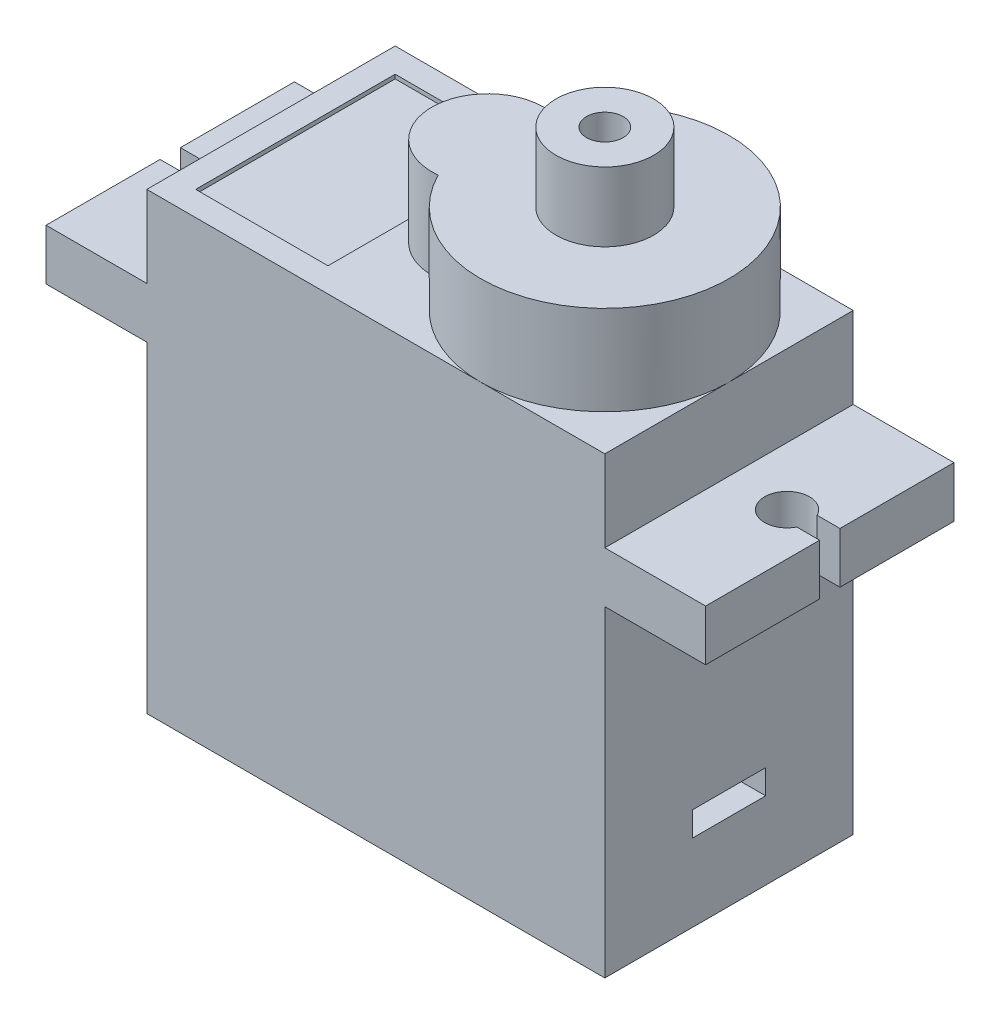
SolidWorks part; units mm, degrees
ref_plane "前视基准面" through (0, 0, 0) normal (0, 0, 1) x (1, 0, 0)
ref_plane "上视基准面" through (0, 0, 0) normal (0, 1, 0) x (1, 0, 0)
ref_plane "右视基准面" through (0, 0, 0) normal (1, 0, 0) x (0, 0, -1)
other "Configuration Table"
sketch "草图1" plane through (0, 0, 0) normal (0, 0, 1) x (1, 0, 0)
  line L0 (-11.25, 0) -> (11.25, 0)
  line L1 (11.25, 0) -> (11.25, 15.8)
  line L2 (11.25, 15.8) -> (16.2, 15.8)
  line L3 (16.2, 15.8) -> (16.2, 18.3)
  line L4 (16.2, 18.3) -> (11.25, 18.3)
  line L5 (11.25, 18.3) -> (11.25, 22.3)
  line L6 (11.25, 22.3) -> (-11.25, 22.3)
  line L7 (-11.25, 22.3) -> (-11.25, 18.3)
  line L8 (-11.25, 18.3) -> (-16.2, 18.3)
  line L9 (-16.2, 18.3) -> (-16.2, 15.8)
  line L10 (-16.2, 15.8) -> (-11.25, 15.8)
  line L11 (-11.25, 15.8) -> (-11.25, 0)
  line L12 (0, 22.3) -> (0, 0) construction
  point P20 (16.2, 17.05)
  dimension "D1" = 22.3
  dimension "D2" = 22.5
  dimension "D3" = 2.5
  dimension "D4" = 32.4
  dimension "D5" = 4
extrude "凸台-拉伸1" add sketch "草图1" along normal blind 12.2
sketch "草图3" plane through (11.25, 0, 0) normal (1, 0, 0) x (0, 0, -1)
  line L0 (-12.2, 0) -> (0, 0) construction
  line L1 (-7.9, 5) -> (-4.3, 5)
  line L2 (-7.9, 5) -> (-7.9, 3.8)
  line L3 (-7.9, 3.8) -> (-4.3, 3.8)
  line L4 (-4.3, 5) -> (-4.3, 3.8)
  line L5 (-6.1, 15.8) -> (-6.1, 0) construction
  line L6 (-12.2, 15.8) -> (0, 15.8) construction
  point P10 (-6.1, 5)
  dimension "D1" = 5
  dimension "D2" = 1.2
  dimension "D3" = 3.6
extrude "切除-拉伸1" cut sketch "草图3" against normal blind 2
sketch "草图4" plane through (0, 22.3, 0) normal (0, 1, 0) x (1, 0, 0)
  line L0 (11.25, 0) -> (-11.25, 0) construction
  line L1 (11.25, -12.2) -> (-11.25, -12.2) construction
  line L2 (11.25, -12.2) -> (11.25, 0) construction
  line L3 (-11.25, -6.1) -> (11.25, -6.1) construction
  line L4 (-11.25, -12.2) -> (-11.25, 0) construction
  line L5 (-3.35, 0) -> (-3.35, -12.2) construction
  line L7 (-10.05, -1.2) -> (-3.55, -1.2)
  line L8 (-10.05, -1.2) -> (-10.05, -11)
  line L9 (-10.05, -11) -> (-3.55, -11)
  line L10 (-3.55, -1.2) -> (-3.55, -11)
  circle A0 centre (5.15, -6.1) radius 6.1
  circle A1 centre (-0.6, -6.1) radius 2.75
  point P20 (-6.8, -1.2)
  dimension "D2" = 5.5
  dimension "D1" = 14.6
  dimension "D3" = 1.2
  dimension "D4" = 1.2
  dimension "D5" = 1.2
  dimension "D6" = 0.2
extrude "凸台-拉伸2" add sketch "草图4" along normal blind 4.4 contours A0 A1 | A0 A1 | A1 A0 region at (5.7152, 22.3, 6.1) region at (0.4853, 22.3, 6.1) region at (-1.8325, 22.3, 6.1)
extrude "切除-拉伸2" cut sketch "草图4<3>" against normal blind 0.2 contours L10 L7 L8 L9 region at (-6.8, 22.3, 6.1)
sketch "草图4<3>" plane through (0, 22.3, 0) normal (0, 1, 0) x (1, 0, 0) same geometry as "草图4"
sketch "草图5" plane through (0, 26.7, 0) normal (0, 1, 0) x (1, 0, 0)
  circle A0 centre (5.15, -6.1) radius 2.4
  arc A1 (-0.303, -8.8339) -> (-0.303, -3.3661) centre (5.15, -6.1) ccw construction
  circle A2 centre (5.15, -6.1) radius 0.9
  dimension "D1" = 4.8
  dimension "D2" = 1.8
extrude "凸台-拉伸3" add sketch "草图5" along normal blind 3.4
sketch "草图6" plane through (0, 18.3, 0) normal (0, 1, 0) x (1, 0, 0)
  line L0 (-13, 0) -> (-13, -12.2) construction
  line L1 (-11.25, 0) -> (-16.2, 0) construction
  line L2 (-11.25, -12.2) -> (-16.2, -12.2) construction
  line L3 (-16.2, -12.2) -> (-16.2, 0) construction
  line L4 (-16.2, -6.1) -> (-13, -6.1) construction
  line L5 (-15.0798, -5.6) -> (-16.2, -5.6)
  line L6 (-15.0798, -6.6) -> (-16.2, -6.6)
  line L7 (-15.6399, -5.6) -> (-15.6399, -6.6) construction
  circle A0 centre (-14.1, -6.1) radius 1.1
  point P16 (-15.6399, -6.6)
  point P19 (-15.6399, -6.1)
  line M6 (-16.2, 0) -> (-16.2, -12.2)
  dimension "D1" = 2.2
  dimension "D3" = 1
  dimension "D2" = 3.2
extrude "切除-拉伸3" cut sketch "草图6" against normal up to next contours A0 L5 L6 M6 | A0 region at (-15.6798, 18.3, 6.1)
mirror "镜向1" about plane through (0, 0, 0) normal (1, 0, 0) of "切除-拉伸3"
